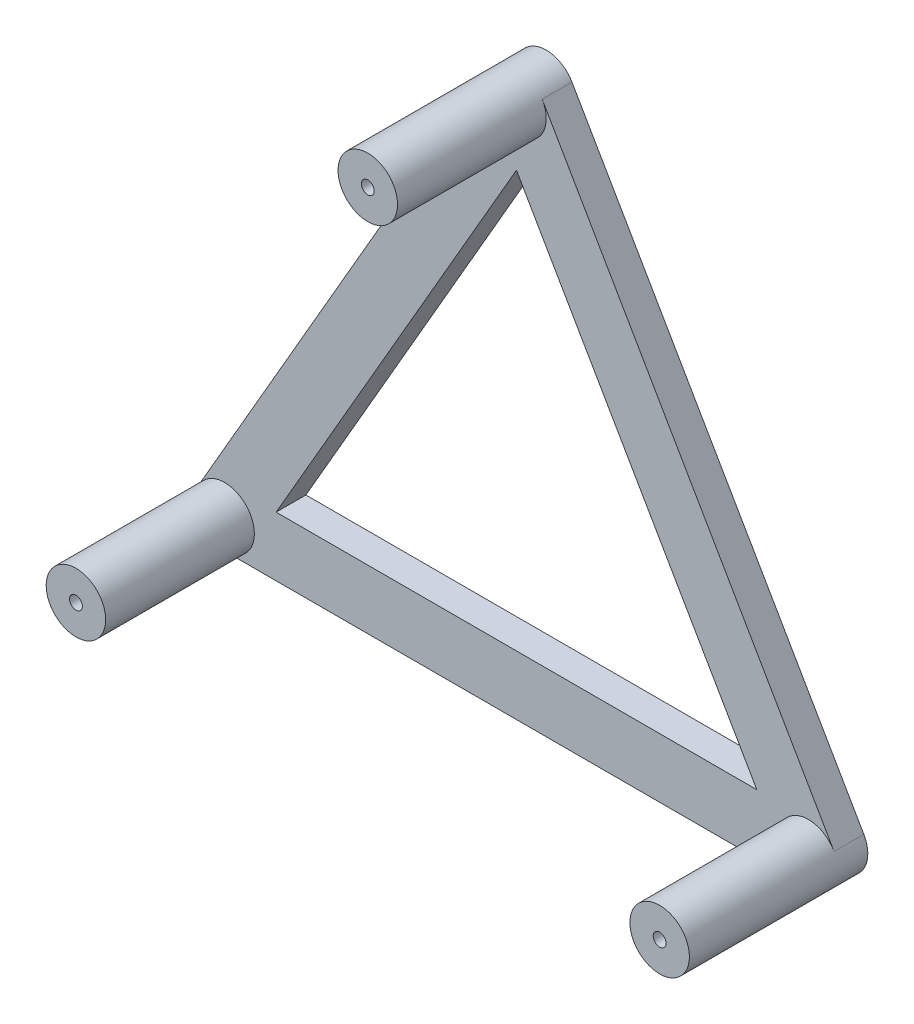
SolidWorks part; units mm, degrees
ref_plane "前视基准面" through (0, 0, 0) normal (0, 0, 1) x (1, 0, 0)
ref_plane "上视基准面" through (0, 0, 0) normal (0, 1, 0) x (1, 0, 0)
ref_plane "右视基准面" through (0, 0, 0) normal (1, 0, 0) x (0, 0, -1)
other "Configuration Table"
sketch "草图1" plane through (0, 0, 0) normal (0, 0, 1) x (1, 0, 0)
  line L3 (0, 0) -> (0, -30) construction
  line L5 (-2.5981, 35.5) -> (-32.0429, -15.5)
  line L6 (-29.4449, -20) -> (29.4449, -20)
  line L11 (0, 0) -> (-29.4449, -17) construction
  line L12 (0, 0) -> (29.4449, -17) construction
  line L13 (32.0429, -15.5) -> (2.5981, 35.5)
  line L14 (2.5981, 32.5) -> (-26.8468, -18.5)
  line L15 (-29.4449, -14) -> (29.4449, -14)
  line L16 (-2.5981, 32.5) -> (26.8468, -18.5)
  circle A8 centre (0, 0) radius 34 construction
  circle A18 centre (0, 34) radius 0.65
  circle A19 centre (-29.4449, -17) radius 0.65
  circle A20 centre (29.4449, -17) radius 0.65
  circle A21 centre (-29.4449, -17) radius 3
  circle A22 centre (29.4449, -17) radius 3
  circle A23 centre (0, 34) radius 3
  dimension "D1" = 68
  dimension "D2" = 6
  dimension "D4" = 120
  dimension "D7" = 120
  dimension "D8" = 1.3
extrude "凸台-拉伸1" add sketch "草图1" along normal blind 3 contours A23 L5 A21 L15 L14 L16 | A23 L14 L16 L15 A22 L13 | A23 L16 L14 | A22 L16 L15 L14 A21 L6 | A21 L14 L15 | A22 L15 L16 | A23 | A21 | A22 region at (-14.7872, 8.5374, 0) region at (14.7872, 8.5374, 0) region at (0, 30.2064, 0) region at (-26.1595, -15.1032, 0) region at (0, -17.0748, 0) region at (26.1595, -15.1032, 0)
extrude "凸台-拉伸2" add sketch "草图1<6>" along normal blind 15 from surface contours A21 | A23 | A22 starting at face at (0, 0, 3)
sketch "草图1<6>" plane through (0, 0, 0) normal (0, 0, 1) x (1, 0, 0) same geometry as "草图1"
extrude "切除-拉伸2" cut sketch "草图1<7>" against normal blind 2 from surface contours A18 | A19 | A20 region at (0, 34, 0) starting at face at (3, 34, 18)
sketch "草图1<7>" plane through (0, 0, 0) normal (0, 0, 1) x (1, 0, 0) same geometry as "草图1"
sketch "草图2" plane through (0, 0, 0) normal (0, 0, -1) x (-1, 0, 0)
  line L0 (0, -14) -> (0, -20) construction
  line L1 (24.2487, -14) -> (-24.2487, -14) construction
  line L2 (29.4449, -20) -> (-29.4449, -20) construction
  line L3 (-13.6654, -17) -> (0, -17) construction
  line L4 (0, -17) -> (13.6654, -17) construction
  line L5 (0, 34) -> (-13.6654, -17) construction
  line L6 (0, 34) -> (13.6654, -17) construction
  circle A0 centre (-13.6654, -17) radius 0.75
  circle A1 centre (13.6654, -17) radius 0.75
  circle A2 centre (0, 34) radius 0.75
  arc A5 (2.5981, 35.5) -> (-2.5981, 35.5) centre (0, 34) ccw construction
  dimension "D1" = 1.5
  dimension "D2" = 15
extrude "切除-拉伸3" cut sketch "草图2" against normal blind 2
